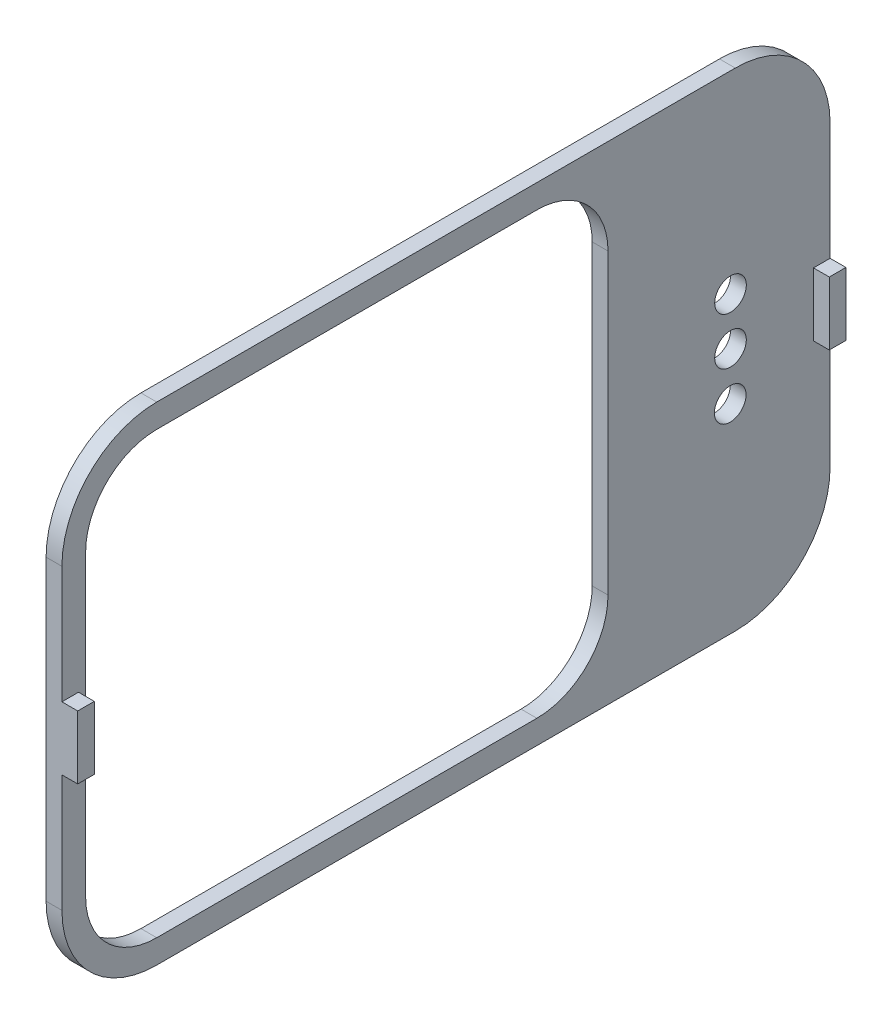
SolidWorks part; units mm, degrees
ref_plane "前视基准面" through (0, 0, 0) normal (0, 0, 1) x (1, 0, 0)
ref_plane "上视基准面" through (0, 0, 0) normal (0, 1, 0) x (1, 0, 0)
ref_plane "右视基准面" through (0, 0, 0) normal (1, 0, 0) x (0, 0, -1)
other "Configuration Table"
sketch "草图1" plane through (0, 0, 0) normal (1, 0, 0) x (0, 0, -1)
  line L16 (26.8102, -0.1143) -> (26.8102, 18.7357)
  line L17 (-15.7898, -6.1143) -> (20.8102, -6.1143)
  line L18 (-21.7898, 18.7357) -> (-21.7898, -0.1143)
  line L19 (20.8102, 24.7357) -> (-15.7898, 24.7357)
  arc A12 (20.8102, -6.1143) -> (26.8102, -0.1143) centre (20.8102, -0.1143) ccw
  arc A13 (-21.7898, -0.1143) -> (-15.7898, -6.1143) centre (-15.7898, -0.1143) ccw
  arc A14 (-15.7898, 24.7357) -> (-21.7898, 18.7357) centre (-15.7898, 18.7357) ccw
  arc A15 (26.8102, 18.7357) -> (20.8102, 24.7357) centre (20.8102, 18.7357) ccw
  dimension "D2" = 6
  dimension "D1" = 30.85
  dimension "D3" = 48.6
extrude "凸台-拉伸1" add sketch "草图1" along normal blind 1
sketch "草图2" plane through (0, 0, 0) normal (-1, 0, 0) x (0, 0, 1)
  line L2 (15.7898, -6.1143) -> (-20.8102, -6.1143) construction
  line L7 (21.7898, 18.7357) -> (21.7898, -0.1143) construction
  line L8 (-20.8102, 24.7357) -> (15.7898, 24.7357) construction
  line L12 (-12.7598, 18.7357) -> (-12.7598, -0.1143)
  line L13 (15.7898, 23.2357) -> (-8.2598, 23.2357)
  line L15 (-8.2598, -4.6143) -> (15.7898, -4.6143)
  line L126 (20.2898, 18.7357) -> (20.2898, -0.1143)
  arc A0 (15.7898, -4.6143) -> (20.2898, -0.1143) centre (15.7898, -0.1143) ccw
  arc A1 (-12.7598, -0.1143) -> (-8.2598, -4.6143) centre (-8.2598, -0.1143) ccw
  arc A2 (15.7898, 23.2357) -> (20.2898, 18.7357) centre (15.7898, 18.7357) cw
  arc A3 (-12.7598, 18.7357) -> (-8.2598, 23.2357) centre (-8.2598, 18.7357) cw
  dimension "D2" = 1.5
  dimension "D1" = 4.5
  dimension "D3" = 1.5
  dimension "D4" = 1.5
extrude "切除-拉伸1" cut sketch "草图2" against normal through all
sketch "草图3" plane through (0, 0, 0) normal (-1, 0, 0) x (0, 0, 1)
  line L0 (-27.1453, 9.5025) -> (-34.4305, 9.5025) construction
  circle A1 centre (-20.4913, 6.4943) radius 1
  circle A3 centre (-20.5098, 9.5025) radius 1
  circle A4 centre (-20.4913, 6.4943) radius 1
  circle A5 centre (-20.5098, 12.5025) radius 1
  circle A6 centre (-20.5098, 9.5025) radius 1
  circle A7 centre (-20.5098, 12.5025) radius 1
extrude "切除-拉伸2" cut sketch "草图3" against normal through all contours A3 | A5 | A1
sketch "草图4" plane through (1, 0, 0) normal (1, 0, 0) x (0, 0, -1)
  line L1 (-20.7398, 7.3107) -> (-21.7898, 7.3107)
  line L2 (-20.7398, 7.3107) -> (-20.7398, 11.3107)
  line L3 (-20.7398, 11.3107) -> (-21.7898, 11.3107)
  line L4 (-21.7898, 7.3107) -> (-21.7898, 11.3107)
  line L5 (-21.7898, 18.7357) -> (-21.7898, -0.1143) construction
  line L6 (26.8102, -0.1143) -> (26.8102, 18.7357) construction
  line L7 (26.8102, 7.3107) -> (25.7602, 7.3107)
  line L8 (26.8102, 7.3107) -> (26.8102, 11.3107)
  line L9 (26.8102, 11.3107) -> (25.7602, 11.3107)
  line L10 (25.7602, 7.3107) -> (25.7602, 11.3107)
  line L11 (-21.7898, 18.7357) -> (-21.7898, -0.1143) construction
  point P16 (-21.7898, 9.3107)
  point P17 (-21.7898, 9.3107)
  point P18 (25.7602, 9.3107)
  dimension "D1" = 4
  dimension "D2" = 1.05
extrude "凸台-拉伸2" add sketch "草图4" along normal blind 1
